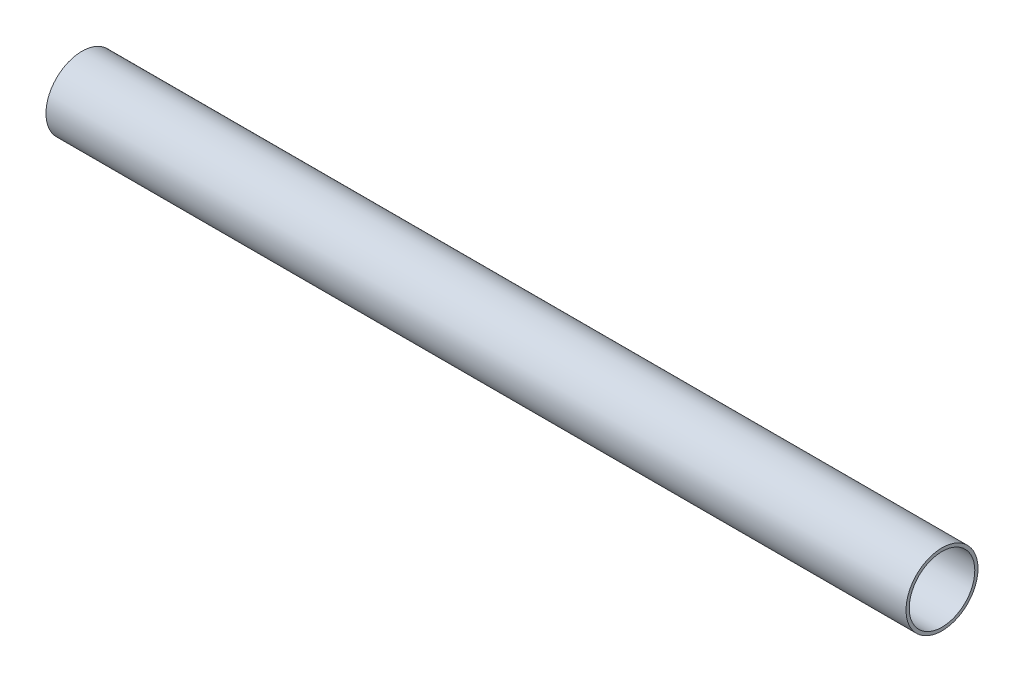
SolidWorks part; units mm, degrees
ref_plane "Vorne" through (0, 0, 0) normal (0, 0, 1) x (1, 0, 0)
ref_plane "Oben" through (0, 0, 0) normal (0, 1, 0) x (1, 0, 0)
ref_plane "Seite" through (0, 0, 0) normal (1, 0, 0) x (0, 0, -1)
sketch "Skizze1" plane through (0, 0, 0) normal (1, 0, 0) x (0, 0, -1)
  circle A0 centre (0, 0) radius 5.1
  circle A1 centre (0, 0) radius 5.6
  dimension "D1" = 10.2
  dimension "D2" = 11.2
extrude "Aufsatz-Linear austragen1" add sketch "Skizze1" along normal blind 133.8
